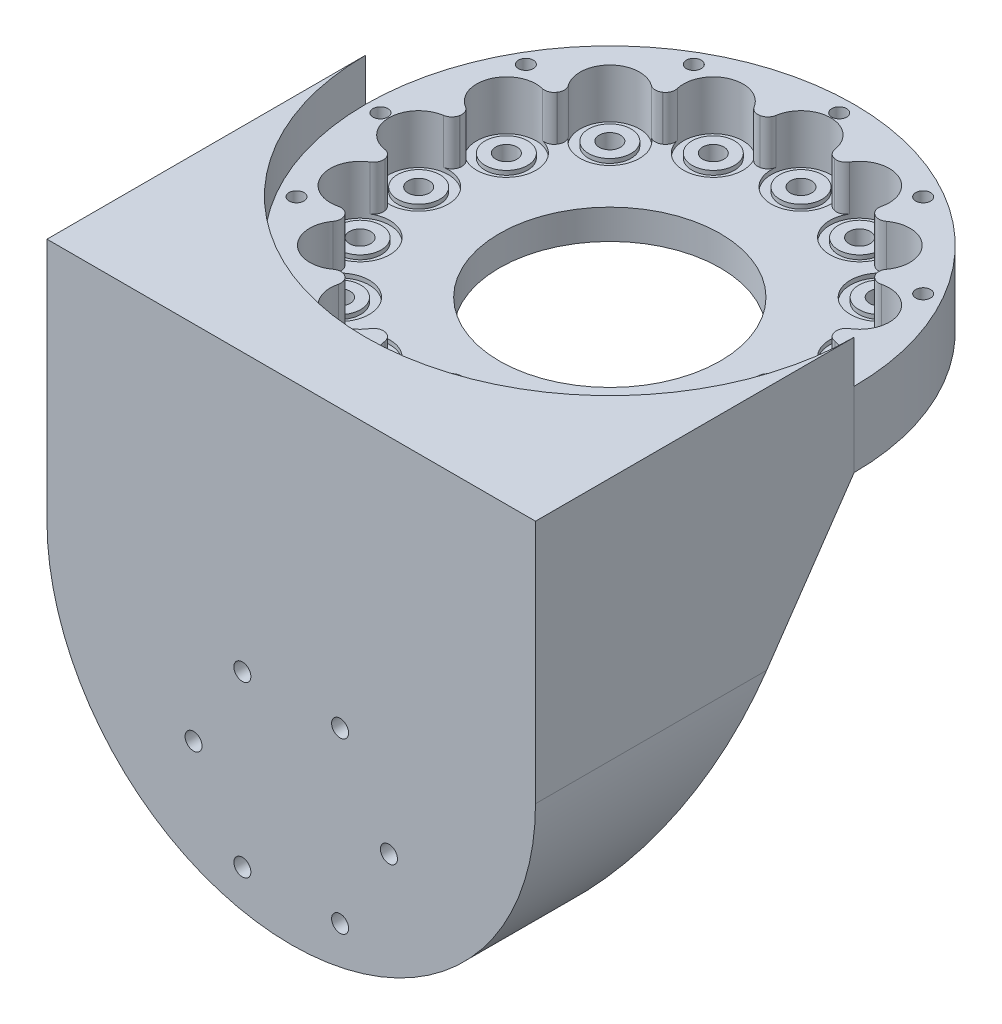
SolidWorks part; units mm, degrees
ref_plane "Front Plane" through (0, 0, 0) normal (0, 0, 1) x (1, 0, 0)
ref_plane "Top Plane" through (0, 0, 0) normal (0, 1, 0) x (1, 0, 0)
ref_plane "Right Plane" through (0, 0, 0) normal (1, 0, 0) x (0, 0, -1)
sketch "Sketch1" plane through (0, 0, 0) normal (0, 1, 0) x (1, 0, 0)
  line L0 (-57.5, 0) -> (57.5, 0) construction
  line L1 (57.5, 0) -> (57.5, -60)
  line L2 (57.5, -60) -> (-57.5, -60)
  line L3 (-57.5, -60) -> (-57.5, 0)
  circle A0 centre (0, 0) radius 57.5
  circle A1 centre (0, 0) radius 54 construction
  circle A2 centre (0, 54) radius 1.75
  circle A3 centre (27, 46.7654) radius 1.75
  circle A4 centre (46.7654, 27) radius 1.75
  circle A5 centre (54, 0) radius 1.75
  circle A6 centre (46.7654, -27) radius 1.75
  circle A7 centre (27, -46.7654) radius 1.75
  circle A8 centre (0, -54) radius 1.75
  circle A9 centre (-27, -46.7654) radius 1.75
  circle A10 centre (-46.7654, -27) radius 1.75
  circle A11 centre (-54, 0) radius 1.75
  circle A12 centre (-46.7654, 27) radius 1.75
  circle A13 centre (-27, 46.7654) radius 1.75
  circle A14 centre (0, 0) radius 26
  circle A15 centre (0, 0) radius 45 construction
  circle A16 centre (0, 45) radius 2.5
  circle A17 centre (17.2208, 41.5746) radius 2.5
  circle A18 centre (31.8198, 31.8198) radius 2.5
  circle A19 centre (41.5746, 17.2208) radius 2.5
  circle A20 centre (45, 0) radius 2.5
  circle A21 centre (41.5746, -17.2208) radius 2.5
  circle A22 centre (31.8198, -31.8198) radius 2.5
  circle A23 centre (17.2208, -41.5746) radius 2.5
  circle A24 centre (0, -45) radius 2.5
  circle A25 centre (-17.2208, -41.5746) radius 2.5
  circle A26 centre (-31.8198, -31.8198) radius 2.5
  circle A27 centre (-41.5746, -17.2208) radius 2.5
  circle A28 centre (-45, 0) radius 2.5
  circle A29 centre (-41.5746, 17.2208) radius 2.5
  circle A30 centre (-31.8198, 31.8198) radius 2.5
  circle A31 centre (-17.2208, 41.5746) radius 2.5
  point P31 (0, 0)
  point P55 (0, 0)
  dimension "D1" = 115
  dimension "D2" = 108
  dimension "D3" = 3.5
  dimension "D4" = 52
  dimension "D5" = 90
  dimension "D6" = 5
  dimension "D8" = 60
  dimension "D7" = 16
extrude "Boss-Extrude1" add sketch "Sketch1" along normal blind 7 contours A0 A31 A30 A29 A28 A27 A26 A25 A24 A23 A22 A21 A20 A19 A18 A17 A16 A14 A13 A12 A11 A10 A9 A8 A7 | A0 L3 L2 L1
sketch "Sketch3" plane through (0, 7, 0) normal (0, 1, 0) x (1, 0, 0)
  line L0 (-57.5, 0) -> (-57.5, -60)
  line L1 (-57.5, -60) -> (57.5, -60)
  line L2 (57.5, -60) -> (57.5, 0)
  circle A0 centre (0, 0) radius 57.5
  circle A1 centre (0, 0) radius 45
  circle A2 centre (0, 45) radius 7
  circle A3 centre (17.2208, 41.5746) radius 7
  circle A4 centre (31.8198, 31.8198) radius 7
  circle A5 centre (41.5746, 17.2208) radius 7
  circle A6 centre (45, 0) radius 7
  circle A7 centre (41.5746, -17.2208) radius 7
  circle A8 centre (31.8198, -31.8198) radius 7
  circle A9 centre (17.2208, -41.5746) radius 7
  circle A10 centre (0, -45) radius 7
  circle A11 centre (-17.2208, -41.5746) radius 7
  circle A12 centre (-31.8198, -31.8198) radius 7
  circle A13 centre (-41.5746, -17.2208) radius 7
  circle A14 centre (-45, 0) radius 7
  circle A15 centre (-41.5746, 17.2208) radius 7
  circle A16 centre (-31.8198, 31.8198) radius 7
  circle A17 centre (-17.2208, 41.5746) radius 7
  point P39 (0, 0)
  dimension "D1" = 16
extrude "Boss-Extrude2" add sketch "Sketch3" along normal blind 10.6
sketch "Sketch2" plane through (0, 7, 0) normal (0, 1, 0) x (1, 0, 0)
  circle A0 centre (0, 0) radius 45 construction
  circle A1 centre (0, 45) radius 7
  circle A2 centre (17.2208, 41.5746) radius 7
  circle A3 centre (31.8198, 31.8198) radius 7
  circle A4 centre (41.5746, 17.2208) radius 7
  circle A5 centre (45, 0) radius 7
  circle A6 centre (41.5746, -17.2208) radius 7
  circle A7 centre (31.8198, -31.8198) radius 7
  circle A8 centre (17.2208, -41.5746) radius 7
  circle A9 centre (0, -45) radius 7
  circle A10 centre (-17.2208, -41.5746) radius 7
  circle A11 centre (-31.8198, -31.8198) radius 7
  circle A12 centre (0, 45) radius 5
  circle A13 centre (17.2208, 41.5746) radius 5
  circle A14 centre (31.8198, 31.8198) radius 5
  circle A15 centre (41.5746, 17.2208) radius 5
  circle A16 centre (45, 0) radius 5
  circle A17 centre (41.5746, -17.2208) radius 5
  circle A18 centre (31.8198, -31.8198) radius 5
  circle A19 centre (17.2208, -41.5746) radius 5
  circle A20 centre (0, -45) radius 5
  circle A21 centre (-17.2208, -41.5746) radius 5
  circle A22 centre (-31.8198, -31.8198) radius 5
  circle A23 centre (-41.5746, -17.2208) radius 5
  circle A24 centre (-45, 0) radius 5
  circle A25 centre (-41.5746, 17.2208) radius 5
  circle A26 centre (-31.8198, 31.8198) radius 5
  circle A27 centre (-17.2208, 41.5746) radius 5
  circle A28 centre (-41.5746, -17.2208) radius 7
  circle A29 centre (-45, 0) radius 7
  circle A30 centre (-41.5746, 17.2208) radius 7
  circle A31 centre (-31.8198, 31.8198) radius 7
  circle A32 centre (-17.2208, 41.5746) radius 7
  point P28 (0, 0)
  point P51 (0, 0)
  dimension "D1" = 14
  dimension "D3" = 10
  dimension "D2" = 16
  dimension "D4" = 16
extrude "Cut-Extrude1" cut sketch "Sketch2" against normal blind 1
fillet "Fillet2" radius 2.3 32 edges at (-36.3696, 12.3, -26.5001) (-26.5001, 12.3, -36.3696) (-43.7422, 12.3, -10.5648) (-38.4009, 12.3, -23.46) (-44.4556, 12.3, 6.9788) (-44.4556, 12.3, -6.9788) (-38.4009, 12.3, 23.46) (-43.7422, 12.3, 10.5648) (-26.5001, 12.3, 36.3696) (-36.3696, 12.3, 26.5001) (-10.5648, 12.3, 43.7422) (-23.46, 12.3, 38.4009) (6.9788, 12.3, 44.4556) (-6.9788, 12.3, 44.4556) (23.46, 12.3, 38.4009) (10.5648, 12.3, 43.7422) (36.3696, 12.3, 26.5001) (26.5001, 12.3, 36.3696) (43.7422, 12.3, 10.5648) (38.4009, 12.3, 23.46) (44.4556, 12.3, -6.9788) (44.4556, 12.3, 6.9788) (38.4009, 12.3, -23.46) (43.7422, 12.3, -10.5648) (26.5001, 12.3, -36.3696) (36.3696, 12.3, -26.5001) (-23.46, 12.3, -38.4009) (-10.5648, 12.3, -43.7422) (-6.9788, 12.3, -44.4556) (6.9788, 12.3, -44.4556) (10.5648, 12.3, -43.7422) (23.46, 12.3, -38.4009)
sketch "Sketch5" plane through (57.5, 0, 0) normal (1, 0, 0) x (0, 0, -1)
  line L0 (-60, 17.6) -> (-60, 27.6)
  line L1 (-60, 27.6) -> (0, 27.6)
  line L3 (-60, 0) -> (-60, -87.5)
  line L4 (-60, -87.5) -> (0, 0)
  line L5 (-60, 27.6) -> (-75, 27.6)
  line L6 (-75, 27.6) -> (-75, -87.5)
  line L7 (-75, -87.5) -> (-60, -87.5)
  line L8 (-60, 27.6) -> (-60, -87.5)
  line L9 (0, 27.6) -> (0, 17.6)
  line L10 (0, 17.6) -> (-60, 17.6)
  line M3 (-60, 0) -> (0, 0)
  line M5 (0, 17.6) -> (-60, 17.6)
  line M6 (-60, 17.6) -> (-60, 0)
  dimension "D1" = 87.5
  dimension "D2" = 10
  dimension "D3" = 15
extrude "Boss-Extrude3" add sketch "Sketch5" against normal blind 115 contours L3 L4 M3 | L1 L0 M5 | L6 L7 L3 L0 L5 M6
sketch "Sketch6" plane through (0, -87.5, 0) normal (0, -1, 0) x (1, 0, 0)
  circle A0 centre (0, 0) radius 57.5
extrude "Cut-Extrude2" cut sketch "Sketch6" against normal blind 87.5
sketch "Sketch8" plane through (0, 27.6, 0) normal (0, 1, 0) x (1, 0, 0)
  circle A0 centre (0, 0) radius 57.5
extrude "Cut-Extrude3" cut sketch "Sketch8" against normal blind 10
sketch "Sketch9" plane through (0, 0, 75) normal (0, 0, 1) x (1, 0, 0)
  line L0 (0, 31.965) -> (0, -96.2651) construction
  line L1 (-57.5, -87.5) -> (57.5, -87.5) construction
  circle A0 centre (0, -57.5) radius 30 construction
  circle A1 centre (0, -57.5) radius 23 construction
  circle A2 centre (23, -57.5) radius 2
  circle A3 centre (11.5, -77.4186) radius 2
  circle A4 centre (-11.5, -77.4186) radius 2
  circle A5 centre (-23, -57.5) radius 2
  circle A6 centre (-11.5, -37.5814) radius 2
  circle A7 centre (11.5, -37.5814) radius 2
  point P22 (0, -57.5)
  dimension "D1" = 60
  dimension "D2" = 46
  dimension "D3" = 4
  dimension "D4" = 6
extrude "Cut-Extrude5" cut sketch "Sketch9" against normal blind 50
fillet "Fillet3" radius 57.5 2 edges at (57.5, -87.5, 67.5) (-57.5, -87.5, 67.5)
sketch "Sketch10" plane through (0, 0, 0) normal (0, 0, 1) x (1, 0, 0)
  line L0 (0, 33.065) -> (0, -96.5793) construction
  circle A0 centre (0, -57.5) radius 23 construction
  circle A1 centre (11.5, -37.5814) radius 2 construction
  circle A2 centre (-11.5, -37.5814) radius 2 construction
  circle A3 centre (23, -57.5) radius 4.25
  circle A4 centre (11.5, -77.4186) radius 4.25
  circle A5 centre (-11.5, -77.4186) radius 4.25
  circle A6 centre (-23, -57.5) radius 4.25
  circle A7 centre (-11.5, -37.5814) radius 4.25
  circle A8 centre (11.5, -37.5814) radius 4.25
  point P25 (0, -57.5)
  dimension "D1" = 46
  dimension "D2" = 8.5
  dimension "D3" = 6
extrude "Cut-Extrude6" cut sketch "Sketch10" along normal blind 60
